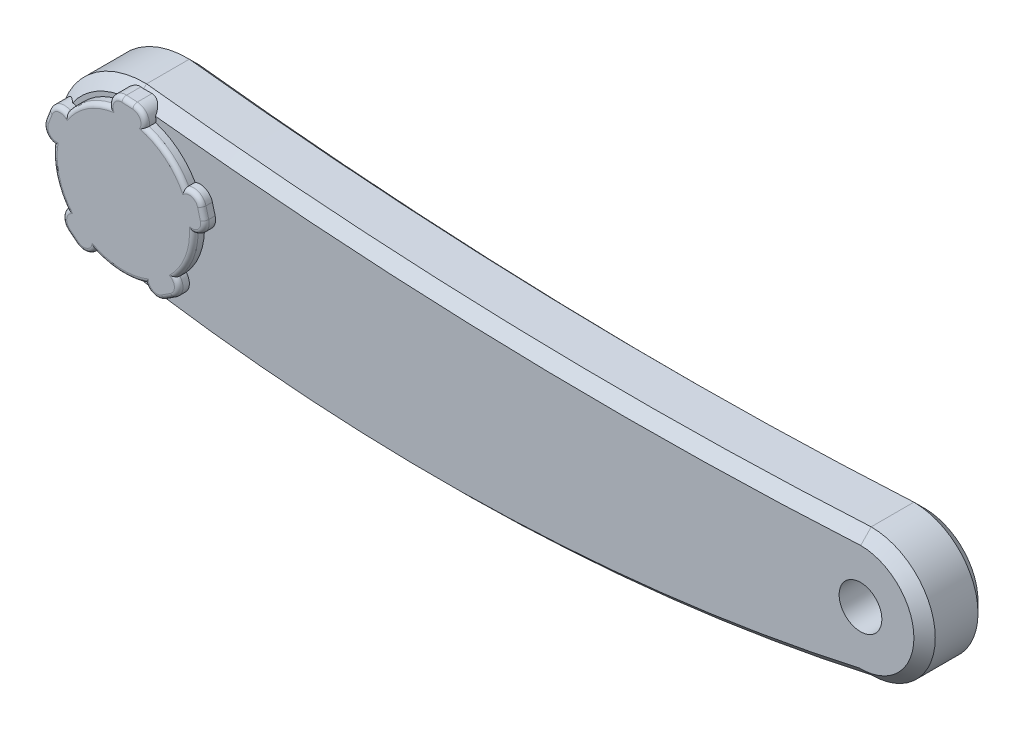
SolidWorks part; units mm, degrees
ref_plane "Front Plane" through (0, 0, 0) normal (0, 0, 1) x (1, 0, 0)
ref_plane "Top Plane" through (0, 0, 0) normal (0, 1, 0) x (1, 0, 0)
ref_plane "Right Plane" through (0, 0, 0) normal (1, 0, 0) x (0, 0, -1)
sketch "Sketch2" plane through (0, 0, 0) normal (0, 0, 1) x (1, 0, 0)
  line L0 (-85, 0) -> (85, 0) construction
  circle A0 centre (85, 0) radius 15
  circle A1 centre (-85, 0) radius 20
  arc A2 (85, 15) -> (-84.5589, 19.9951) centre (29.5612, 1013.4621) cw
  arc A3 (85, -15) -> (-90.7174, -19.1654) centre (-13.3176, 424.1283) cw
  point P4 (0, 0)
  dimension "D2" = 40
  dimension "D3" = 30
  dimension "D4" = 450
  dimension "D5" = 1000
  dimension "D1" = 170
extrude "Boss-Extrude1" add sketch "Sketch2" along normal mid plane 15
chamfer "Chamfer1" distance 2.5 angle 45 8 edges at (100, 0, -7.5) (0.1144, 13.8957, -7.5) (-104.7572, 3.1071, -7.5) (-2.6534, -25.7453, -7.5) (-104.7572, 3.1071, 7.5) (0.1144, 13.8957, 7.5) (100, 0, 7.5) (-2.6534, -25.7453, 7.5)
sketch "Sketch3" plane through (0, 0, 7.5) normal (0, 0, 1) x (1, 0, 0)
  circle A0 centre (-85, 0) radius 16.5
  dimension "D1" = 33
extrude "Boss-Extrude2" add sketch "Sketch3" along normal mid plane 5
sketch "Sketch4" plane through (0, 0, 10) normal (0, 0, 1) x (1, 0, 0)
  line L0 (-85, 0) -> (-68.9097, 0)
  line L1 (-66.0119, 3.7765) -> (-66.6676, 6.2235)
  line L2 (-71.0654, 8.0452) -> (-85, 0)
  line L3 (-66.3397, 5) -> (-85, 0) construction
  line L4 (-73.0426, -10.7665) -> (-85, 0)
  line L5 (-85, 0) -> (-80.0278, -15.3028)
  line L6 (-75.5407, -16.8918) -> (-73.416, -15.512)
  line L7 (-91.5445, -14.6992) -> (-85, 0)
  line L8 (-85, 0) -> (-98.0173, -9.4577)
  line L9 (-98.142, -14.2161) -> (-96.1731, -15.8105)
  line L10 (-101.0022, 1.6819) -> (-85, 0)
  line L11 (-85, 0) -> (-98.0173, 9.4577)
  line L12 (-102.5814, 8.1057) -> (-103.4893, 5.7406)
  line L13 (-88.3454, 15.7387) -> (-85, 0)
  line L14 (-85, 0) -> (-80.0278, 15.3028)
  line L15 (-82.724, 19.2257) -> (-85.2539, 19.3583)
  arc A0 (-66.0119, 3.7765) -> (-68.9097, 0) centre (-68.9097, 3) cw
  arc A1 (-66.6676, 6.2235) -> (-71.0654, 8.0452) centre (-69.5654, 5.4471) ccw
  arc A2 (-73.416, -15.512) -> (-73.0426, -10.7665) centre (-75.05, -12.996) ccw
  arc A3 (-75.5407, -16.8918) -> (-80.0278, -15.3028) centre (-77.1746, -14.3758) cw
  arc A4 (-96.1731, -15.8105) -> (-91.5445, -14.6992) centre (-94.2852, -13.479) ccw
  arc A5 (-98.142, -14.2161) -> (-98.0173, -9.4577) centre (-96.254, -11.8847) cw
  arc A6 (-103.4893, 5.7406) -> (-101.0022, 1.6819) centre (-100.6886, 4.6655) ccw
  arc A7 (-102.5814, 8.1057) -> (-98.0173, 9.4577) centre (-99.7807, 7.0306) cw
  arc A8 (-85.2539, 19.3583) -> (-88.3454, 15.7387) centre (-85.4109, 16.3624) ccw
  arc A9 (-82.724, 19.2257) -> (-80.0278, 15.3028) centre (-82.881, 16.2299) cw
  circle A10 centre (-85, 0) radius 2
  point P6 (-65, 0)
  point P11 (-67.6795, 10)
  point P38 (-85, 0)
  circle M27 centre (-85, 0) radius 16.5
  dimension "D4" = 3
  dimension "D6" = 4
  dimension "D1" = 30
  dimension "D2" = 20
  dimension "D3" = 20
  dimension "D5" = 5
extrude "Boss-Extrude3" add sketch "Sketch4" against normal blind 5 contours A10 L14 A9 A8 L13 M27 | A9 L15 A8 M27 | L3 A10 L0 A0 M27 | L3 A1 L2 A10 M27 | L1 L3 A0 M27 | A10 L11 A7 A6 L10 M27 | A10 L8 A5 A4 L7 M27 | A5 L9 A4 M27 | A10 L5 A3 A2 L4 M27 | A3 L6 A2 M27
fillet "Fillet1" radius 1 20 edges at (-87.5535, 18.4623, 10) (-83.9889, 19.292, 10) (-80.5307, 18.0943, 10) (-74.6162, 12.8229, 10) (-68.2303, 8.1337, 10) (-66.3397, 5, 10) (-66.4102, 1.3409, 10) (-69.5959, -5.9131, 10) (-72.0823, -13.4355, 10) (-74.4784, -16.2019, 10) (-77.9802, -17.2656, 10) (-85.8635, -16.4774, 10) (-93.7861, -16.4372, 10) (-97.1575, -15.0133, 10) (-99.2513, -12.0116, 10) (-100.9378, -4.2705, 10) (-103.3478, 3.2767, 10) (-103.0354, 6.9231, 10) (-100.8276, 9.842, 10) (-93.9865, 13.8381, 10)
sketch "Sketch5" plane through (0, 0, 7.5) normal (0, 0, 1) x (1, 0, 0)
  circle A0 centre (85, 0) radius 5
  dimension "D1" = 10
extrude "Cut-Extrude1" cut sketch "Sketch5" against normal blind 10
sketch "Sketch6" plane through (0, 0, -7.5) normal (0, 0, -1) x (-1, 0, 0)
  circle A0 centre (85, 0) radius 5
  dimension "D1" = 10
extrude "Boss-Extrude4" add sketch "Sketch6" along normal blind 10
